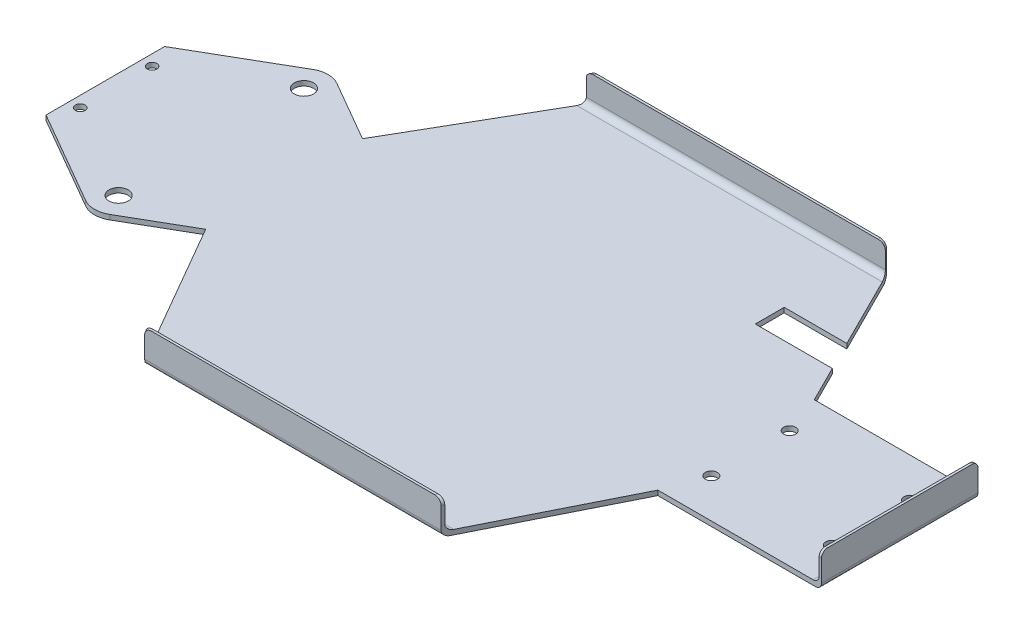
SolidWorks part; units mm, degrees
ref_plane "Front Plane" through (0, 0, 0) normal (0, 0, 1) x (1, 0, 0)
ref_plane "Top Plane" through (0, 0, 0) normal (0, 1, 0) x (1, 0, 0)
ref_plane "Right Plane" through (0, 0, 0) normal (1, 0, 0) x (0, 0, -1)
sketch "Sketch1" plane through (0, 0, 0) normal (0, 1, 0) x (1, 0, 0)
  line L0 (165, 32.5) -> (97, 32.5)
  line L1 (-89.8231, -92.5) -> (67, -92.5)
  line L3 (-56.1347, 92.5) -> (67, 92.5)
  line L4 (165, -32.5) -> (165, 32.5)
  line L5 (-165, -92.5) -> (165, 92.5) construction
  line L6 (-165, 92.5) -> (165, -92.5) construction
  line L7 (97, 32.5) -> (89.5, 47.5)
  line L8 (-187.8754, 0) -> (194.9929, 0) construction
  line L9 (165, -32.5) -> (97, -32.5)
  line L10 (97, -32.5) -> (67, -92.5)
  line L11 (165, 92.5) -> (165, 32.5) construction
  line L12 (67, 92.5) -> (165, 92.5) construction
  line L13 (67, -92.5) -> (165, -92.5) construction
  line L14 (165, -32.5) -> (165, -92.5) construction
  line L16 (103, -16.25) -> (153, -16.25) construction
  line L17 (103, -16.25) -> (103, 16.25) construction
  line L18 (103, 16.25) -> (153, 16.25) construction
  line L19 (153, -16.25) -> (153, 16.25) construction
  line L20 (103, -16.25) -> (153, 16.25) construction
  line L21 (103, 16.25) -> (153, -16.25) construction
  line L25 (-121, -38.5) -> (-89.8231, -92.5) construction
  line L26 (-56.1347, -92.5) -> (-90.7337, -32.5728)
  line L27 (-90.7337, -32.5728) -> (-116, -47.1603)
  line L28 (-121, 38.5) -> (-121, -38.5) construction
  line L29 (-126, -47.1603) -> (-165, -24.6436)
  line L30 (-90.7337, 32.5728) -> (-116, 47.1603)
  line L31 (-56.1347, 92.5) -> (-90.7337, 32.5728)
  line L32 (-165, -24.6436) -> (-165, 24.6436)
  line L33 (-89.8231, -92.5) -> (-165, -92.5) construction
  line L34 (-165, -92.5) -> (-165, 92.5) construction
  line L35 (-165, 92.5) -> (-56.1347, 92.5) construction
  line L36 (-165, 24.6436) -> (-126, 47.1603)
  line L37 (57.5, 47.5) -> (57.5, 59.5)
  line L38 (57.5, 59.5) -> (83.5, 59.5)
  line L39 (57.5, 47.5) -> (89.5, 47.5)
  line L40 (83.5, 59.5) -> (67, 92.5)
  line L41 (-121, 184.5763) -> (-121, -179.129) construction
  circle A0 centre (-121, 38.5) radius 4
  circle A1 centre (-121, -38.5) radius 4
  circle A2 centre (103, 16.25) radius 2.5
  circle A3 centre (153, 16.25) radius 2.5
  circle A4 centre (103, -16.25) radius 2.5
  circle A5 centre (153, -16.25) radius 2.5
  arc A6 (-126, -47.1603) -> (-116, -47.1603) centre (-121, -38.5) ccw
  arc A7 (-126, 47.1603) -> (-116, 47.1603) centre (-121, 38.5) cw
  circle A8 centre (-121, 0) radius 22.9999 construction
  circle A9 centre (-160.4976, 14.92) radius 2
  circle A10 centre (-160.4976, 14.92) radius 2 construction
  circle A11 centre (-160.4976, -14.92) radius 2
  circle A12 centre (-160.4976, -14.92) radius 2 construction
  point P0 (0, 0)
  point P18 (128, 0)
  dimension "D5" = 8
  dimension "D12" = 5
  dimension "D13" = 5
  dimension "D14" = 5
  dimension "D15" = 5
  dimension "D21" = 10
  dimension "D2" = 185
  dimension "D3" = 65
  dimension "D4" = 30
  dimension "D6" = 330
  dimension "D7" = 54
  dimension "D8" = 68
  dimension "D9" = 32.5
  dimension "D10" = 50
  dimension "D11" = 12
  dimension "D16" = 15
  dimension "D19" = 60
  dimension "D20" = 29.175
  dimension "D22" = 44
  dimension "D23" = 60
  dimension "D24" = 60
  dimension "D25" = 32
  dimension "D27" = 12
extrude "Boss-Extrude1" add sketch "Sketch1" along normal blind 2 contours A7 A6 L27 L26 L1 L10 L9 L4 L0 L7 L3 L31 L30 A5 A4 A3 A2 A0 A1 region at (-1.2674, 0, 0.4579)
sketch "Sketch2" plane through (0, 2, 0) normal (0, 1, 0) x (1, 0, 0)
  line L0 (-56.1347, -92.5) -> (67, -92.5)
  line L1 (67, -92.5) -> (67.5, -91.5)
  line L2 (97, -32.5) -> (67, -92.5) construction
  line L3 (67.5, -91.5) -> (-56.712, -91.5)
  line L4 (-56.1347, -92.5) -> (-90.7337, -32.5728) construction
  line L5 (-56.712, -91.5) -> (-56.1347, -92.5)
  line L6 (-56.1347, 92.5) -> (67, 92.5)
  line L7 (67, 92.5) -> (67.5, 91.5)
  line L8 (83.5, 59.5) -> (67, 92.5) construction
  line L9 (67.5, 91.5) -> (-56.712, 91.5)
  line L10 (-56.1347, 92.5) -> (-90.7337, 32.5728) construction
  line L11 (-56.712, 91.5) -> (-56.1347, 92.5)
  line L16 (165, 32.5) -> (97, 32.5) construction
  line L17 (165, -32.5) -> (164, -32.5)
  line L18 (165, -32.5) -> (165, 32.5)
  line L19 (165, 32.5) -> (164, 32.5)
  line L20 (164, -32.5) -> (164, 32.5)
  dimension "D1" = 1
  dimension "D2" = 1
  dimension "D3" = 1
extrude "Boss-Extrude2" add sketch "Sketch2" along normal blind 12
fillet "Fillet1" radius 2.5 12 edges at (67.25, 14, 92) (-56.4234, 14, 92) (-56.4234, 14, -92) (67.25, 14, -92) (5.394, 2, 91.5) (5.4327, 0, 92.5) (5.4327, 0, -92.5) (5.394, 2, -91.5) (164.5, 14, -32.5) (164, 2, 0) (164.5, 14, 32.5) (165, 0, 0)
